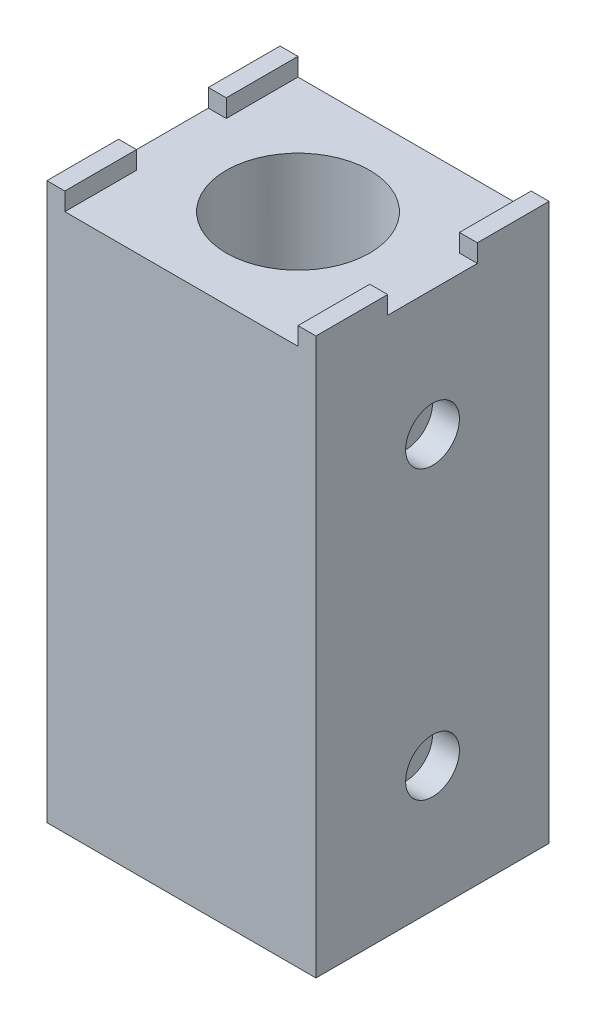
SolidWorks part; units mm, degrees
ref_plane "Front Plane" through (0, 0, 0) normal (0, 0, 1) x (1, 0, 0)
ref_plane "Top Plane" through (0, 0, 0) normal (0, 1, 0) x (1, 0, 0)
ref_plane "Right Plane" through (0, 0, 0) normal (1, 0, 0) x (0, 0, -1)
sketch "Sketch2" plane through (0, 0, 0) normal (0, 1, 0) x (1, 0, 0)
  line L1 (-7.5, 6.5) -> (7.5, 6.5)
  line L2 (-7.5, 6.5) -> (-7.5, -6.5)
  line L3 (-7.5, -6.5) -> (7.5, -6.5)
  line L4 (7.5, 6.5) -> (7.5, -6.5)
  line L5 (-7.5, 6.5) -> (7.5, -6.5) construction
  line L6 (-7.5, -6.5) -> (7.5, 6.5) construction
  point P0 (0, 0)
  dimension "D1" = 13
  dimension "D2" = 15
extrude "Boss-Extrude1" add sketch "Sketch2" along normal blind 30
sketch "Sketch3" plane through (0, 30, 0) normal (0, 1, 0) x (1, 0, 0)
  line L1 (7.5, 6.5) -> (6.5, 6.5)
  line L2 (7.5, 6.5) -> (7.5, 2.5)
  line L3 (7.5, 2.5) -> (6.5, 2.5)
  line L4 (6.5, 6.5) -> (6.5, 2.5)
  line L5 (7.5, -6.5) -> (6.5, -6.5)
  line L6 (7.5, -6.5) -> (7.5, -2.5)
  line L7 (7.5, -2.5) -> (6.5, -2.5)
  line L8 (6.5, -6.5) -> (6.5, -2.5)
  line L9 (-7.5, -6.5) -> (-6.5, -6.5)
  line L10 (-7.5, -6.5) -> (-7.5, -2.5)
  line L11 (-7.5, -2.5) -> (-6.5, -2.5)
  line L12 (-6.5, -6.5) -> (-6.5, -2.5)
  line L13 (-7.5, 6.5) -> (-6.5, 6.5)
  line L14 (-7.5, 6.5) -> (-7.5, 2.5)
  line L15 (-7.5, 2.5) -> (-6.5, 2.5)
  line L16 (-6.5, 6.5) -> (-6.5, 2.5)
  dimension "D1" = 4
  dimension "D2" = 4
  dimension "D3" = 4
  dimension "D4" = 4
  dimension "D5" = 1
  dimension "D6" = 1
  dimension "D7" = 1
  dimension "D8" = 1
extrude "Boss-Extrude2" add sketch "Sketch3" along normal blind 1
sketch "Sketch4" plane through (0, 30, 0) normal (0, 1, 0) x (1, 0, 0)
  circle A0 centre (0, 0) radius 4
  dimension "D1" = 8
extrude "Cut-Extrude3" cut sketch "Sketch4" against normal blind 22
sketch "Sketch5" plane through (0, 8, 0) normal (0, 1, 0) x (1, 0, 0)
  circle A0 centre (0, 0) radius 2
  dimension "D1" = 4
extrude "Cut-Extrude4" cut sketch "Sketch5" against normal blind 5
sketch "Sketch7" plane through (0, 3, 0) normal (0, 1, 0) x (1, 0, 0)
  circle A0 centre (0, 0) radius 1.5
  dimension "D1" = 3
extrude "Cut-Extrude5" cut sketch "Sketch7" against normal through all
fillet "Fillet4" radius 3 1 edges at (0, 8, 2) first distance on face at (0, 8, 2)
fillet "Fillet5" radius 3 1 edges at (0, 3, 1.5) first distance on face at (0, 3, 1.5)
hole_wizard "Ø8.0 (3) Diameter Hole1" positions "3DSketch4" profile "Sketch10" hole size "Ø8.0" standard "ANSI Metric"
sketch3d "3DSketch4"
  line L0 (7.5, 31, -6.5) -> (7.5, 0, -6.5) construction
  line L1 (7.5, 0, 6.5) -> (7.5, 0, -6.5) construction
  line L2 (7.5, 30, 2.5) -> (7.5, 30, -2.5) construction
  point P0 (7.5, 7, 0)
  point P2 (7.5, 23, 0)
  dimension "D1" = 6.5
  dimension "D2" = 7
  dimension "D3" = 7
  dimension "D4" = 6.5
sketch "Sketch10" plane through (7.5, 7, 0) normal (0, 1, 0) x (0, 0, -1)
  line L0 (0, 0) -> (0, 1.5)
  line L1 (0, 1.5) -> (1.5, 1.5)
  line L2 (1.5, 1.5) -> (1.5, 0)
  line L5 (1.5, 0) -> (0, 0)
  line L10 (0, 1.5) -> (-1.5, 1.5) construction
  line L11 (0, -6.35) -> (0, 107.95) construction
  dimension "Hole Dia." = 3
  dimension "Hole Depth" = 1.5
  dimension "Drill Angle" = 180
